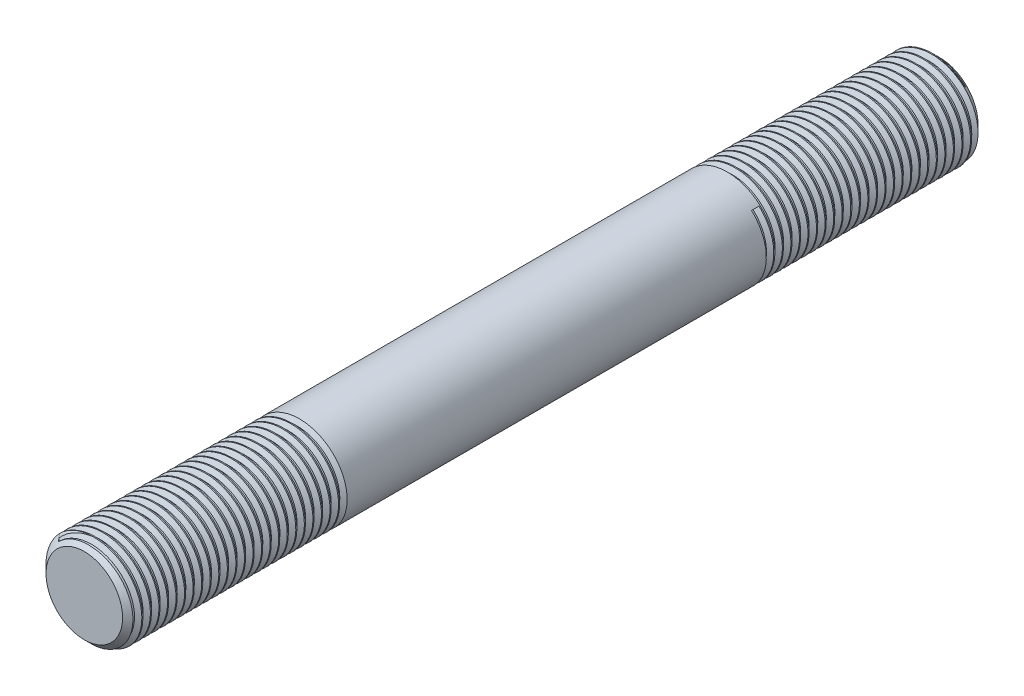
SolidWorks part; units mm, degrees
ref_plane "Front Plane" through (0, 0, 0) normal (0, 0, 1) x (1, 0, 0)
ref_plane "Top Plane" through (0, 0, 0) normal (0, 1, 0) x (1, 0, 0)
ref_plane "Right Plane" through (0, 0, 0) normal (1, 0, 0) x (0, 0, -1)
sketch "Sketch1" plane through (0, 0, 0) normal (0, 0, 1) x (1, 0, 0)
  circle A0 centre (0, 0) radius 10.95
  dimension "D1" = 21.9
extrude "Boss-Extrude1" add sketch "Sketch1" along normal mid plane 200
chamfer "Chamfer1" distance 2 angle 45 2 edges at (10.95, 0, -100) (10.95, 0, 100)
thread "Thread1" pitch 2 method cut profile "Thread Profile1" start angle 45, offset 0, length 50, pitch 2, diameter 21.9
ref_plane "Plane1" through (-7.7428, 7.7428, 100) normal (-0.7071, -0.7071, 0) x (-0.7071, 0.7071, 0)
sketch "Thread Profile1" plane through (-7.7428, 7.7428, 100) normal (-0.7071, -0.7071, 0) x (-0.7071, 0.7071, 0)
  line L0 (0, 0) -> (0, 2) construction
  line L11 (0, 0) -> (0, 1.75)
  line L12 (0, 1.75) -> (-1.0825, 1.125)
  line L13 (-1.0825, 1.125) -> (-1.0825, 0.625)
  line L15 (-1.0825, 0.625) -> (0, 0)
  line L17 (-1.0825, 0.875) -> (0, 0.875) construction
  point P2 (0, 0)
  dimension "Pitch" = 2
  dimension "Profile_Angle" = 60
  dimension "Profile_Land" = 0.5
  dimension "Profile_Height" = 1.0825
thread "Thread2" pitch 2 method cut profile "Thread Profile2" start angle 45, offset 0, length 50, pitch 2, diameter 21.9
ref_plane "Plane2" through (7.7428, 7.7428, -100) normal (0.7071, -0.7071, 0) x (0.7071, 0.7071, 0)
sketch "Thread Profile2" plane through (7.7428, 7.7428, -100) normal (0.7071, -0.7071, 0) x (0.7071, 0.7071, 0)
  line L0 (0, 0) -> (0, 2) construction
  line L11 (0, 0) -> (0, 1.75)
  line L12 (0, 1.75) -> (-1.0825, 1.125)
  line L13 (-1.0825, 1.125) -> (-1.0825, 0.625)
  line L15 (-1.0825, 0.625) -> (0, 0)
  line L17 (-1.0825, 0.875) -> (0, 0.875) construction
  point P2 (0, 0)
  dimension "Pitch" = 2
  dimension "Profile_Angle" = 60
  dimension "Profile_Land" = 0.5
  dimension "Profile_Height" = 1.0825
